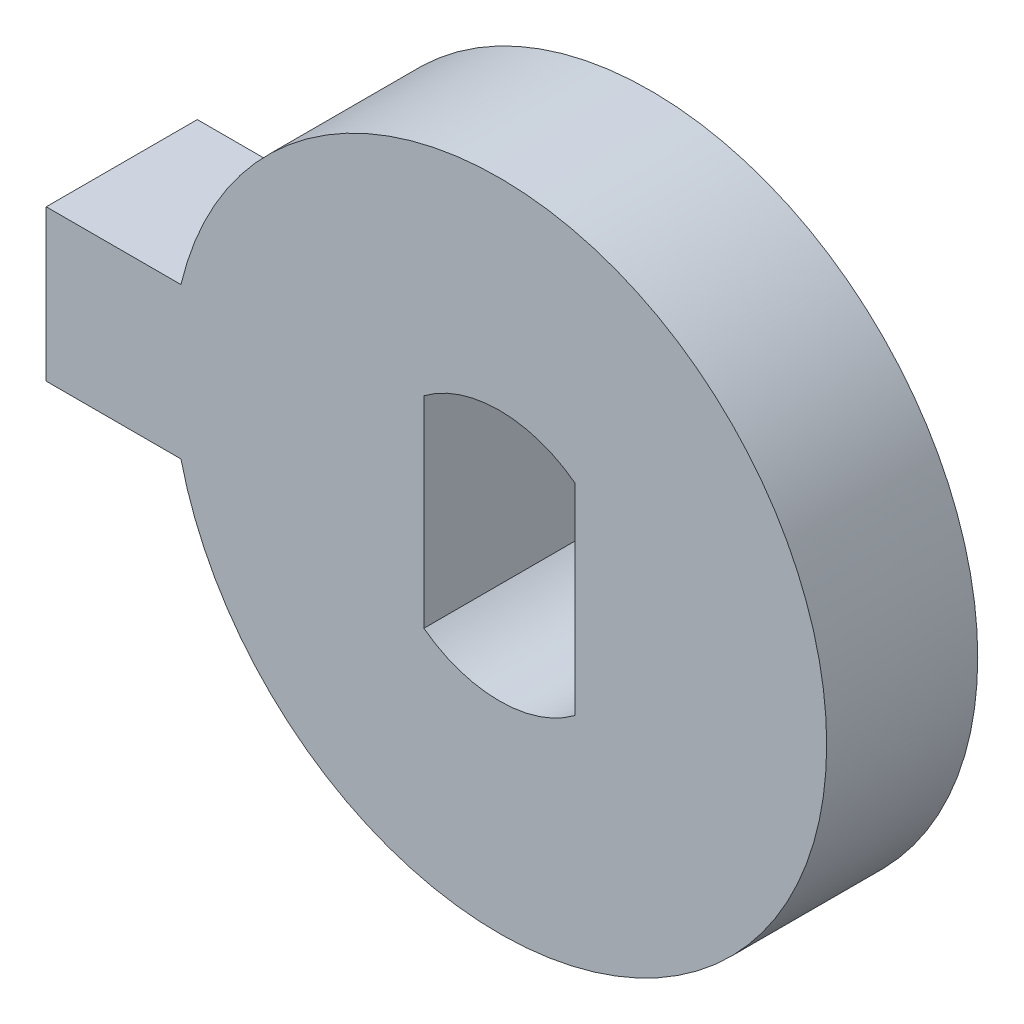
SolidWorks part; units mm, degrees
ref_plane "Спереди" through (0, 0, 0) normal (0, 0, 1) x (1, 0, 0)
ref_plane "Сверху" through (0, 0, 0) normal (0, 1, 0) x (1, 0, 0)
ref_plane "Справа" through (0, 0, 0) normal (1, 0, 0) x (0, 0, -1)
other "Configuration Table"
sketch "Эскиз1" plane through (0, 0, 0) normal (0, 0, 1) x (1, 0, 0)
  line L0 (-1.5, 2) -> (-1.5, -2) construction
  line L1 (-1.5, 0) -> (-1.5, 2)
  line L2 (-1.5, 0) -> (-1.5, -2)
  line L3 (1.5, -2) -> (1.5, 2)
  line L4 (-6.3246, 1.5) -> (-1.5, 1.5) construction
  line L5 (-9, 1.5) -> (-6.3246, 1.5)
  line L6 (-9, 1.5) -> (-9, -1.5)
  line L7 (-9, -1.5) -> (-6.3246, -1.5)
  line L10 (-6.3246, -1.5) -> (-1.5, -1.5) construction
  line L12 (1.5, -2) -> (1.5, 2) construction
  arc A0 (-6.3246, -1.5) -> (-6.3246, 1.5) centre (0, 0) ccw
  arc A1 (-1.5, -2) -> (1.5, -2) centre (0, 0) ccw
  arc A2 (1.5, 2) -> (-1.5, 2) centre (0, 0) ccw
  arc A3 (-6.3246, 1.5) -> (-6.3246, -1.5) centre (0, 0) ccw construction
  arc A4 (1.5, 2) -> (-1.5, 2) centre (0, 0) ccw construction
  point P6 (0, 0)
  point P12 (1.5, 0)
  point P14 (-1.5, 0)
  point P16 (-6.3246, 1.5)
  point P17 (-6.3246, -1.5)
  point P22 (1.5, 0)
  dimension "D1" = 0
  dimension "D3" = 0
  dimension "D4" = 6.5
  dimension "D2" = 0
  dimension "D5" = 9
  dimension "D6" = 1.5
  dimension "D7" = 1.5
extrude "Бобышка-Вытянуть1" add sketch "Эскиз1" along normal blind 3
